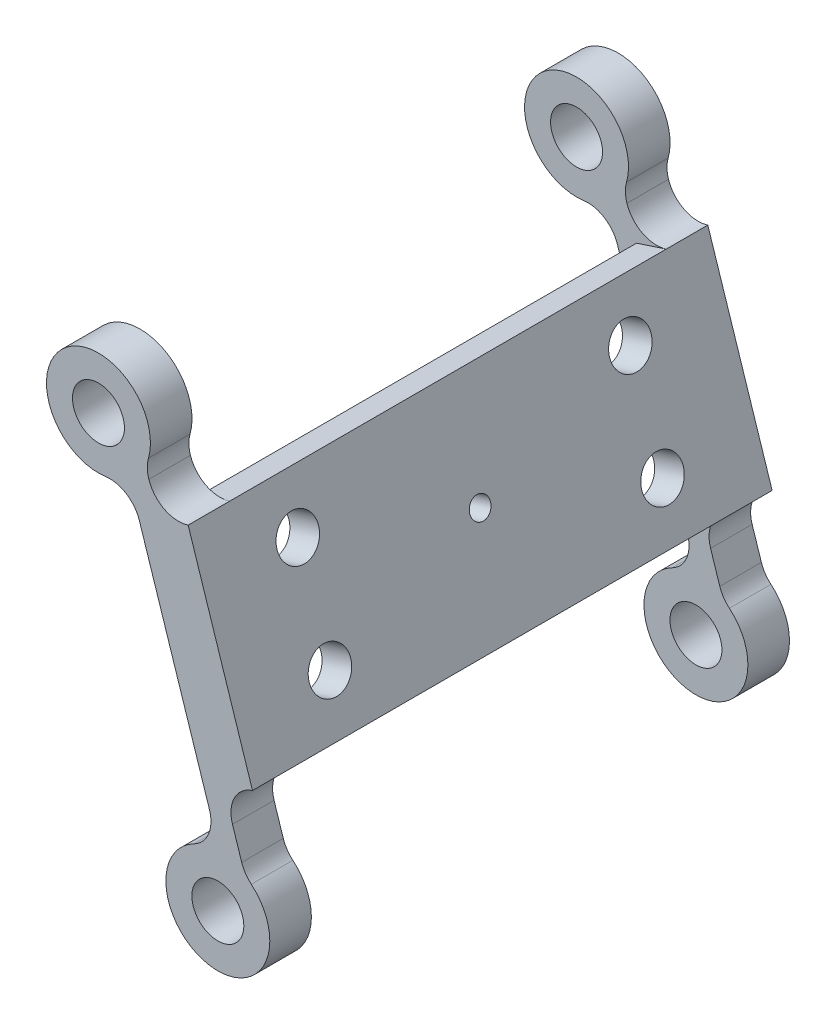
SolidWorks part; units mm, degrees
ref_plane "Front Plane" through (0, 0, 0) normal (0, 0, 1) x (1, 0, 0)
ref_plane "Top Plane" through (0, 0, 0) normal (0, 1, 0) x (1, 0, 0)
ref_plane "Right Plane" through (0, 0, 0) normal (1, 0, 0) x (0, 0, -1)
sketch "Sketch1" plane through (0, 0, 0) normal (0, 0, 1) x (1, 0, 0)
  line L2 (-17.3976, 40.0711) -> (-7.8424, 10.7162)
  line L3 (-10.6381, 12.6112) -> (-10.2569, 11.44)
  line L4 (-18.7542, 37.5449) -> (-10.6381, 12.6112)
  line L5 (-18.7542, 37.5449) -> (-18.9568, 38.1671)
  circle A0 centre (-21.9266, 42.1896) radius 2.5
  arc A2 (-17.3976, 40.0711) -> (-18.9568, 38.1671) centre (-21.9266, 42.1896) ccw
  arc A3 (-10.2569, 11.44) -> (-7.8424, 10.7162) centre (-10.4388, 6.4433) ccw
  circle A5 centre (-10.4388, 6.4433) radius 2.5
extrude "Boss-Extrude1" add sketch "Sketch1" along normal blind 4 contours L2 L4 A0 A5 region at (-13.1006, 25.2372, 0)
sketch "Sketch2" plane through (0, 0, 4) normal (0, 0, 1) x (1, 0, 0)
  line L0 (-16.1484, 36.2334) -> (-9.958, 17.2156)
  line L1 (-16.1484, 36.2334) -> (-13.2958, 37.162)
  line L2 (-9.958, 17.2156) -> (-7.1053, 18.1442)
  line L3 (-13.2958, 37.162) -> (-7.1053, 18.1442)
  line L4 (-17.3976, 40.0711) -> (-7.8424, 10.7162) construction
  dimension "D1" = 3
  dimension "D2" = 20
extrude "Boss-Extrude2" add sketch "Sketch2" against normal blind 50
ref_plane "Plane1" through (0, 0, -21) normal (0, 0, 1) x (1, 0, 0)
mirror "Mirror1" about plane through (0, 0, -21) normal (0, 0, 1) of "Boss-Extrude1"
sketch "Sketch3" plane through (-3.937, -1.2815, 0) normal (-0.9509, -0.3095, 0) x (0, 0, 1)
  line L0 (0, 39.4524) -> (0, 34.4524) construction
  line L1 (0, 34.4524) -> (-5, 34.4524) construction
  line L2 (0, 29.4524) -> (-10.938, 29.4524) construction
  line L3 (0, 39.4524) -> (0, 19.4524) construction
  line L4 (-21, 19.4524) -> (-21, 39.4524) construction
  line L7 (-42, 19.4524) -> (0, 19.4524) construction
  line L8 (-42, 39.4524) -> (0, 39.4524) construction
  circle A0 centre (-5, 34.4524) radius 2
  circle A1 centre (-5, 24.4524) radius 2
  circle A2 centre (-37, 24.4524) radius 2
  circle A3 centre (-37, 34.4524) radius 2
  circle A4 centre (-21, 29.4524) radius 1
extrude "Cut-Extrude1" cut sketch "Sketch3" against normal blind 10
fillet "Fillet1" radius 3 12 edges at (-9.958, 17.2156, 2) (-9.958, 17.2156, -44) (-16.1484, 36.2334, -44) (-16.1484, 36.2334, 2) (-10.2569, 11.44, 2) (-7.8424, 10.7162, 2) (-7.8424, 10.7162, -44) (-10.2569, 11.44, -44) (-18.9568, 38.1671, -44) (-17.3976, 40.0711, -44) (-17.3976, 40.0711, 2) (-18.9568, 38.1671, 2)
ref_plane "Plane2" through (0, 0, -21) normal (0, 0, -1) x (-1, 0, 0)
